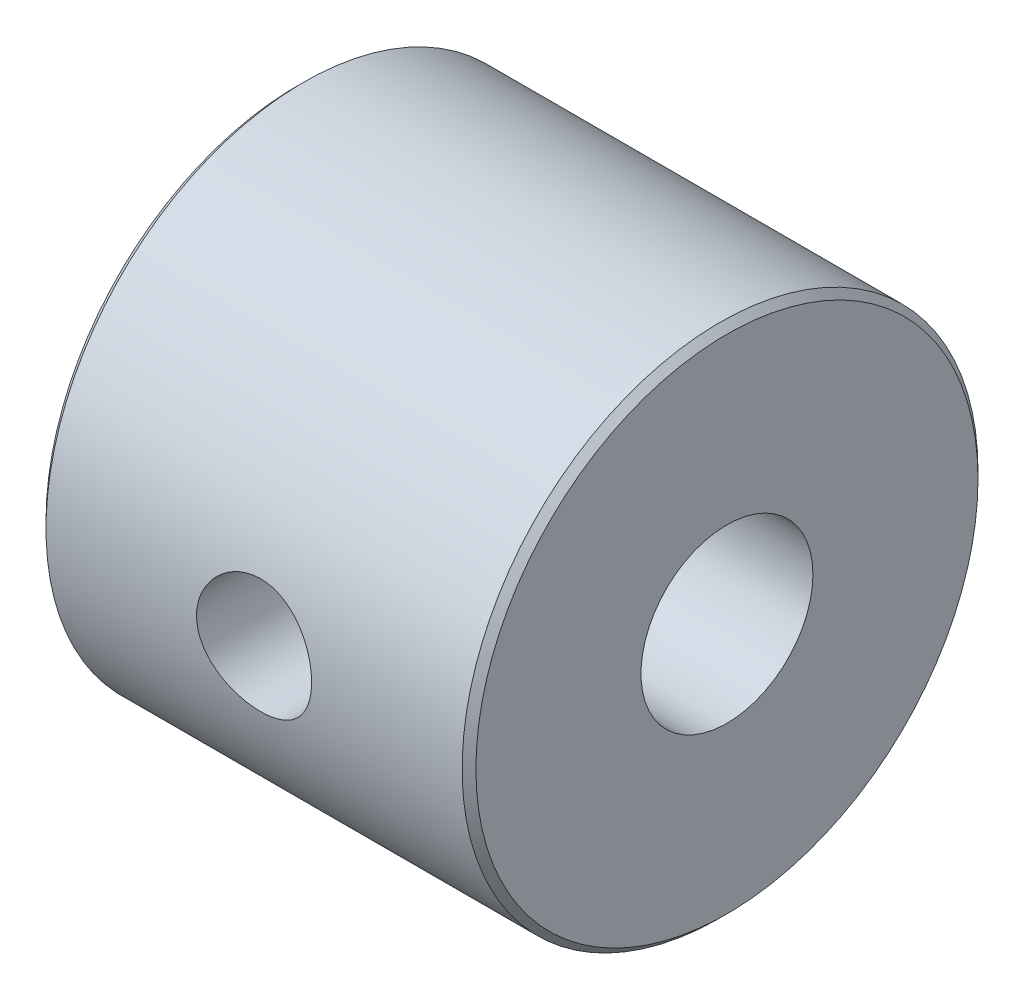
SolidWorks part; units mm, degrees
ref_plane "Front Plane" through (0, 0, 0) normal (0, 0, 1) x (1, 0, 0)
ref_plane "Top Plane" through (0, 0, 0) normal (0, 1, 0) x (1, 0, 0)
ref_plane "Right Plane" through (0, 0, 0) normal (1, 0, 0) x (0, 0, -1)
sketch "Sketch1" plane through (0, 0, 0) normal (1, 0, 0) x (0, 0, -1)
  circle A0 centre (0, 0) radius 19.05
  circle A1 centre (0, 0) radius 6.35
  dimension "D1" = 38.1
  dimension "D2" = 12.7
extrude "Boss-Extrude1" add sketch "Sketch1" along normal blind 31.75
sketch "Sketch2" plane through (0, 0, 0) normal (0, 0, 1) x (1, 0, 0)
  line L0 (0, 0) -> (15.875, 0) construction
  circle A0 centre (15.875, 0) radius 4.25
  circle A1 centre (15.875, 0) radius 2.5
  dimension "D1" = 8.5
  dimension "D2" = 5
  dimension "D3" = 15.875
extrude "Cut-Extrude1" cut sketch "Sketch2" along normal through all contours A0
extrude "Cut-Extrude3" cut sketch "Sketch2<6>" against normal through all contours A1
sketch "Sketch2<6>" plane through (0, 0, 0) normal (0, 0, 1) x (1, 0, 0) same geometry as "Sketch2"
chamfer "Chamfer1" distance 0.508 angle 45 2 edges at (31.75, 0, -19.05) (0, 0, -19.05)
